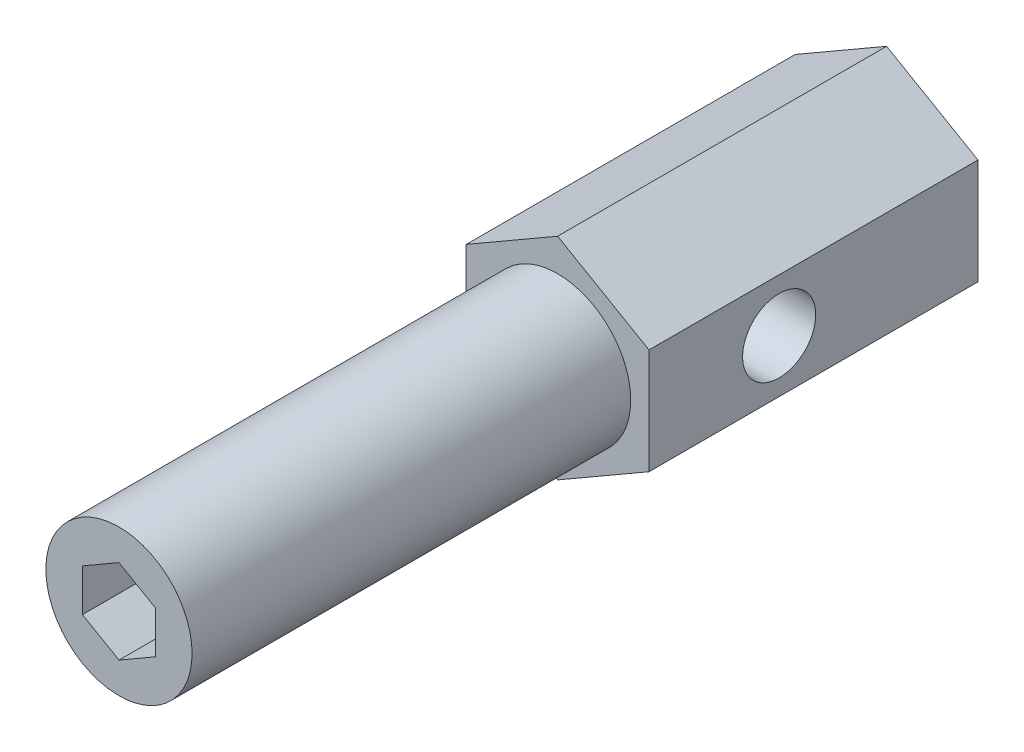
SolidWorks part; units mm, degrees
ref_plane "Front Plane" through (0, 0, 0) normal (0, 0, 1) x (1, 0, 0)
ref_plane "Top Plane" through (0, 0, 0) normal (0, 1, 0) x (1, 0, 0)
ref_plane "Right Plane" through (0, 0, 0) normal (1, 0, 0) x (0, 0, -1)
sketch "Sketch1" plane through (0, 0, 0) normal (0, 0, 1) x (1, 0, 0)
  line L1 (-15.875, 0) -> (15.875, 0) construction
  dimension "Width" = 31.75
sketch "Sketch2" plane through (0, 0, 0) normal (1, 0, 0) x (0, 0, -1)
  line L0 (152.4, 0) -> (-152.4, 0)
  point P4 (0, 0)
  dimension "Length" = 304.8
sketch "Sketch3" plane through (0, 0, 0) normal (0, 0, 1) x (1, 0, 0)
  line L1 (0, 18.3309) -> (-15.875, 9.1654)
  line L2 (-15.875, 9.1654) -> (-15.875, -9.1654)
  line L3 (-15.875, -9.1654) -> (0, -18.3309)
  line L4 (0, -18.3309) -> (15.875, -9.1654)
  line L5 (15.875, -9.1654) -> (15.875, 9.1654)
  line L6 (15.875, 9.1654) -> (0, 18.3309)
  circle A1 centre (0, 0) radius 15.875 construction
extrude "Boss-Extrude1" add sketch "Sketch3" along normal up to vertex (152.4 mm away) and the other way up to vertex (152.4 mm away) up to point (0, 0, 152.4) other way up to point (0, 0, -152.4)
sketch "Sketch4" plane through (0, 0, -152.4) normal (0, 0, -1) x (-1, 0, 0)
  line L1 (0, 18.3309) -> (-15.875, 9.1654)
  line L2 (-15.875, 9.1654) -> (-15.875, -9.1654)
  line L3 (-15.875, -9.1654) -> (0, -18.3309)
  line L4 (0, -18.3309) -> (15.875, -9.1654)
  line L5 (15.875, -9.1654) -> (15.875, 9.1654)
  line L6 (15.875, 9.1654) -> (0, 18.3309)
  circle A0 centre (0, 0) radius 15.875 construction
extrude "Cut-Extrude1" cut sketch "Sketch4" against normal blind 171.45
sketch "Sketch5" plane through (0, 0, 152.4) normal (0, 0, 1) x (1, 0, 0)
  line L1 (0, 7.3323) -> (-6.35, 3.6662)
  line L2 (-6.35, 3.6662) -> (-6.35, -3.6662)
  line L3 (-6.35, -3.6662) -> (0, -7.3323)
  line L4 (0, -7.3323) -> (6.35, -3.6662)
  line L5 (6.35, -3.6662) -> (6.35, 3.6662)
  line L6 (6.35, 3.6662) -> (0, 7.3323)
  circle A0 centre (0, 0) radius 6.35 construction
  dimension "D1" = 12.7
extrude "Cut-Extrude2" cut sketch "Sketch5" against normal blind 40.132
sketch "Sketch6" plane through (0, 0, 152.4) normal (0, 0, 1) x (1, 0, 0)
  circle A0 centre (0, 0) radius 12.7
  circle A1 centre (0, 0) radius 18.3309
  dimension "D1" = 25.4
extrude "Cut-Extrude3" cut sketch "Sketch6" against normal blind 76.2
sketch "Sketch7" plane through (15.875, 0, 0) normal (1, 0, 0) x (0, 0, -1)
  line L0 (-19.05, 9.1654) -> (-19.05, -9.1654) construction
  circle A0 centre (-53.594, 0) radius 6.35
  dimension "D1" = 12.7
  dimension "D2" = 34.544
extrude "Cut-Extrude4" cut sketch "Sketch7" against normal through all
ref_axis "Axis1" through (0, 0, 76.2) along (0, 0, 1)
